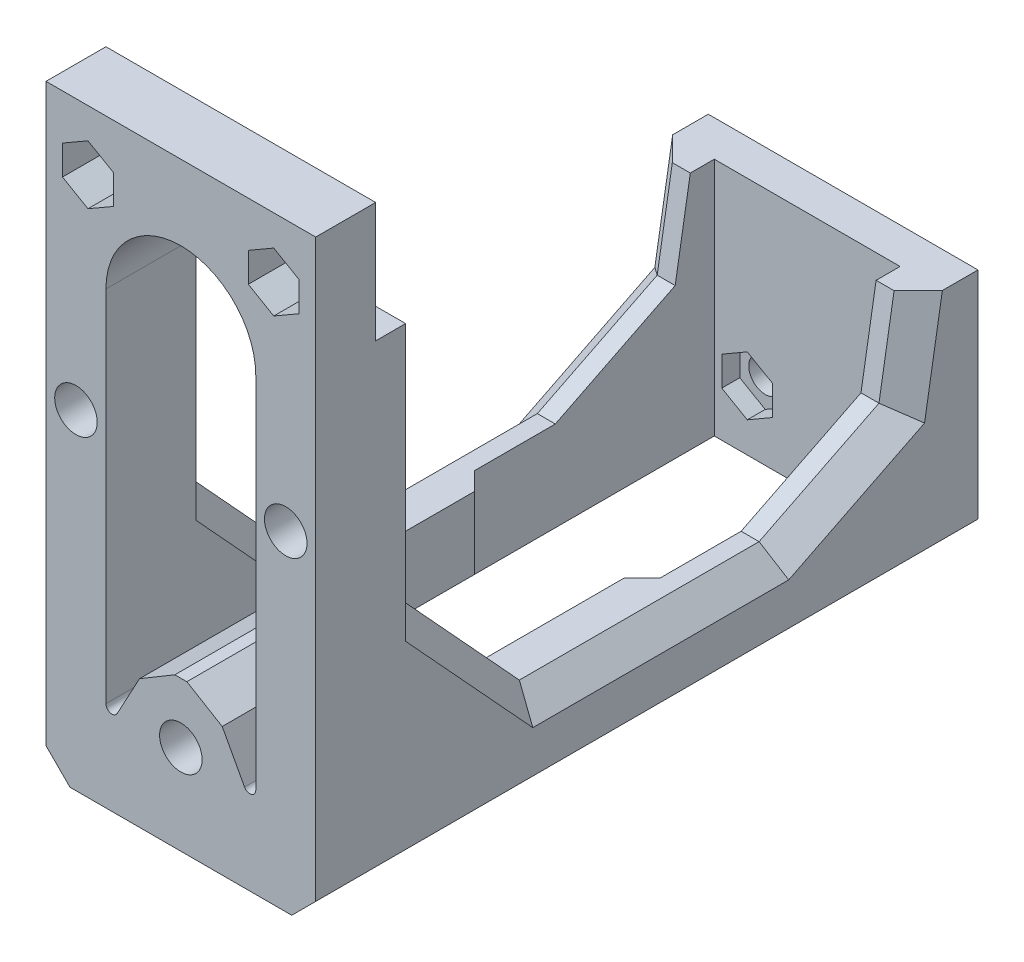
SolidWorks part; units mm, degrees
ref_plane "Front Plane" through (0, 0, 0) normal (0, 0, 1) x (1, 0, 0)
ref_plane "Top Plane" through (0, 0, 0) normal (0, 1, 0) x (1, 0, 0)
ref_plane "Right Plane" through (0, 0, 0) normal (1, 0, 0) x (0, 0, -1)
sketch "Sketch1" plane through (0, 0, 0) normal (0, 1, 0) x (1, 0, 0)
  line L0 (0, 0) -> (0, -29.9339) construction
  line L1 (-22.5, 0) -> (-12.5, 0)
  line L2 (-22.5, 0) -> (-22.5, -110.5)
  line L3 (-22.5, -110.5) -> (-12.5, -110.5)
  line L4 (-12.5, 0) -> (-12.5, -110.5)
  line L5 (-22.5, 0) -> (-12.5, -110.5) construction
  line L6 (-22.5, -110.5) -> (-12.5, 0) construction
  line L7 (22.5, -110.5) -> (12.5, -110.5)
  line L8 (12.5, 0) -> (12.5, -110.5)
  line L9 (22.5, 0) -> (12.5, 0)
  line L10 (22.5, 0) -> (22.5, -110.5)
  point P0 (-17.5, -55.25)
  dimension "D1" = 110.5
  dimension "D2" = 10
  dimension "D3" = 12.5
extrude "Boss-Extrude1" add sketch "Sketch1" along normal blind 100
sketch "Sketch2" plane through (0, 0, 0) normal (0, 0, -1) x (-1, 0, 0)
  line L0 (12.5, 0) -> (22.5, 0) construction
  line L1 (-22.5, 40) -> (22.5, 40)
  line L2 (-22.5, 40) -> (-22.5, 0)
  line L3 (-22.5, 0) -> (22.5, 0)
  line L4 (22.5, 40) -> (22.5, 0)
  line L5 (-22.5, 40) -> (22.5, 0) construction
  line L6 (-22.5, 0) -> (22.5, 40) construction
  line L7 (-22.5, 100) -> (-22.5, 0) construction
  line L8 (22.5, 100) -> (22.5, 0) construction
  point P0 (0, 20)
  dimension "D1" = 40
extrude "Boss-Extrude2" add sketch "Sketch2" against normal blind 6
sketch "Sketch3" plane through (-22.5, 0, 0) normal (-1, 0, 0) x (0, 0, 1)
  line L0 (95.5, 121.1423) -> (95.5, 40)
  line L1 (95.5, 40) -> (72.5237, 15)
  line L2 (72.5237, 15) -> (32.5237, 15)
  line L3 (32.5237, 15) -> (12.5237, 25)
  line L4 (12.5237, 25) -> (10, 40)
  line L5 (10, 40) -> (0, 40)
  line L6 (0, 100) -> (0, 0) construction
  line L7 (0, 0) -> (110.5, 0) construction
  line L8 (110.5, 100) -> (110.5, 0) construction
  line L9 (95.5, 121.1423) -> (-7.9843, 121.1423)
  line L10 (-7.9843, 121.1423) -> (-7.9843, 40)
  line L11 (-7.9843, 40) -> (0, 40)
  dimension "D1" = 40
  dimension "D2" = 15
  dimension "D3" = 25
  dimension "D4" = 20
  dimension "D5" = 10
  dimension "D6" = 15
  dimension "D7" = 40
  dimension "D8" = 40
extrude "Cut-Extrude1" cut sketch "Sketch3" against normal through all both and the other way through all
chamfer "Chamfer1" distance 4 angle 45 10 edges at (-12.5, 27.5, 84.0118) (12.5, 27.5, 84.0118) (22.5, 32.5, 11.2618) (22.5, 27.5, 84.0118) (22.5, 15, 52.5237) (22.5, 20, 22.5237) (-22.5, 32.5, 11.2618) (-22.5, 27.5, 84.0118)
chamfer "Chamfer2" distance 4 angle 45 2 edges at (22.5, 0, 55.25) (-22.5, 0, 55.25)
sketch "Sketch4" plane through (0, 0, 0) normal (0, 0, -1) x (-1, 0, 0)
  line L0 (-18.5, 0) -> (18.5, 0) construction
  line L1 (0, 0) -> (0, 25.518) construction
  circle A0 centre (-10, 10) radius 2.75
  circle A1 centre (10, 10) radius 2.75
  dimension "D3" = 5.5
  dimension "D1" = 10
  dimension "D2" = 10
extrude "Cut-Extrude2" cut sketch "Sketch4" against normal up to surface (6 mm away) and the other way through all up to face at (0, 20, 6)
sketch "Sketch5" plane through (0, 0, 6) normal (0, 0, 1) x (1, 0, 0)
  line L1 (-10, 14.9075) -> (-14.25, 12.4537)
  line L2 (-14.25, 12.4537) -> (-14.25, 7.5463)
  line L3 (-14.25, 7.5463) -> (-10, 5.0925)
  line L4 (-10, 5.0925) -> (-5.75, 7.5463)
  line L5 (-5.75, 7.5463) -> (-5.75, 12.4537)
  line L6 (-5.75, 12.4537) -> (-10, 14.9075)
  line L7 (10, 14.9075) -> (5.75, 12.4537)
  line L8 (5.75, 12.4537) -> (5.75, 7.5463)
  line L9 (5.75, 7.5463) -> (10, 5.0925)
  line L10 (10, 5.0925) -> (14.25, 7.5463)
  line L11 (14.25, 7.5463) -> (14.25, 12.4537)
  line L12 (14.25, 12.4537) -> (10, 14.9075)
  circle A0 centre (-10, 10) radius 4.25 construction
  circle A1 centre (10, 10) radius 4.25 construction
  arc A2 (-12.5, 8.8544) -> (-12.5, 11.1456) centre (-10, 10) ccw construction
  arc A3 (12.5, 11.1456) -> (12.5, 8.8544) centre (10, 10) ccw construction
  dimension "D1" = 8.5
extrude "Cut-Extrude3" cut sketch "Sketch5" against normal offset from surface 3 and the other way blind 10 up to face at (12.75, 10, 0)
sketch "Sketch6" plane through (0, 40, 0) normal (0, 1, 0) x (1, 0, 0)
  line L1 (-15.5, -46) -> (15.5, -46)
  line L2 (-15.5, -46) -> (-15.5, -6)
  line L3 (-15.5, -6) -> (15.5, -6)
  line L4 (15.5, -46) -> (15.5, -6)
  line L5 (-15.5, -46) -> (15.5, -6) construction
  line L6 (-15.5, -6) -> (15.5, -46) construction
  line L7 (-18.5, -12.5237) -> (-18.5, -32.5237) construction
  line L8 (-12.5, -6) -> (12.5, -6) construction
  point P0 (0, -26)
  point P7 (0, 0)
  point P11 (0, 0)
  dimension "D1" = 3
  dimension "D2" = 40
extrude "Cut-Extrude4" cut sketch "Sketch6" against normal through all both and the other way through all
chamfer "Chamfer4" distance 3 angle 45 4 edges at (12.5, 0, 78.25) (12.5, 7.5, 46) (-12.5, 0, 78.25) (-12.5, 7.5, 46)
sketch "Sketch7" plane through (0, 0, 110.5) normal (0, 0, 1) x (1, 0, 0)
  line L0 (-12.5, 100) -> (-12.5, 3) construction
  line L1 (12.5, 100) -> (12.5, 3) construction
  line L2 (-15.5, 40) -> (15.5, 40) construction
  line L3 (-22.5, 100) -> (22.5, 100)
  line L4 (22.5, 100) -> (12.5, 75)
  line L6 (-12.5, 75) -> (-22.5, 100)
  arc A0 (12.5, 75) -> (-12.5, 75) centre (0, 75) ccw
  dimension "D1" = 35
extrude "Boss-Extrude3" add sketch "Sketch7" against normal up to surface (15 mm away) up to face at (17.5, 58.0296, 95.5)
sketch "Sketch8" plane through (0, 0, 110.5) normal (0, 0, 1) x (1, 0, 0)
  line L0 (-22.5, 100) -> (-22.5, 4) construction
  line L1 (-22.5, 100) -> (22.5, 100) construction
  line L2 (22.5, 100) -> (22.5, 4) construction
  circle A0 centre (-15.5, 90) radius 2.75
  circle A1 centre (15.5, 90) radius 2.75
  dimension "D3" = 10
  dimension "D5" = 5.5
  dimension "D1" = 7
  dimension "D2" = 10
  dimension "D4" = 7
extrude "Cut-Extrude5" cut sketch "Sketch8" against normal through all both and the other way through all
sketch "Sketch10" plane through (0, 0, 95.5) normal (0, 0, -1) x (-1, 0, 0)
  line L0 (22.5, 40) -> (-22.5, 40) construction
  line L1 (-12.5, 75) -> (-12.5, 34.0888) construction
  line L2 (12.5, 34.0888) -> (12.5, 75) construction
  circle A0 centre (-17.5, 55) radius 3.55
  circle A1 centre (17.5, 55) radius 3.55
  dimension "D1" = 7.1
  dimension "D2" = 15
  dimension "D3" = 5
  dimension "D4" = 5
extrude "Cut-Extrude7" cut sketch "Sketch10" against normal through all both and the other way through all
sketch "Sketch11" plane through (0, 0, 95.5) normal (0, 0, -1) x (-1, 0, 0)
  circle A0 centre (-17.5, 55) radius 4.5
  circle A1 centre (17.5, 55) radius 4.5
  dimension "D1" = 9
extrude "Cut-Extrude8" cut sketch "Sketch11" against normal offset from surface (6 mm away) 9 up to face at (17.5, 58.55, 110.5)
sketch "Sketch12" plane through (0, 0, 95.5) normal (0, 0, -1) x (-1, 0, 0)
  line L0 (-22.5, 100) -> (22.5, 100) construction
  line L1 (-27.382, 104.523) -> (28.3636, 104.523)
  line L2 (-27.382, 104.523) -> (-27.382, 80)
  line L3 (-27.382, 80) -> (28.3636, 80)
  line L4 (28.3636, 104.523) -> (28.3636, 80)
  line L5 (-27.382, 104.523) -> (28.3636, 80) construction
  line L6 (-27.382, 80) -> (28.3636, 104.523) construction
  point P0 (0.4908, 92.2615)
  dimension "D1" = 20
extrude "Cut-Extrude9" cut sketch "Sketch12" against normal offset from surface (5 mm away) 10 up to face at (17.5, 58.55, 110.5)
sketch "Sketch9" plane through (0, 0, 110.5) normal (0, 0, 1) x (1, 0, 0)
  line L1 (-15.5, 94.9075) -> (-19.75, 92.4537)
  line L2 (-19.75, 92.4537) -> (-19.75, 87.5463)
  line L3 (-19.75, 87.5463) -> (-15.5, 85.0925)
  line L4 (-15.5, 85.0925) -> (-11.25, 87.5463)
  line L5 (-11.25, 87.5463) -> (-11.25, 92.4537)
  line L6 (-11.25, 92.4537) -> (-15.5, 94.9075)
  line L7 (15.5, 94.9075) -> (11.25, 92.4537)
  line L8 (11.25, 92.4537) -> (11.25, 87.5463)
  line L9 (11.25, 87.5463) -> (15.5, 85.0925)
  line L10 (15.5, 85.0925) -> (19.75, 87.5463)
  line L11 (19.75, 87.5463) -> (19.75, 92.4537)
  line L12 (19.75, 92.4537) -> (15.5, 94.9075)
  circle A0 centre (-15.5, 90) radius 4.25 construction
  circle A1 centre (15.5, 90) radius 4.25 construction
  dimension "D1" = 8.5
extrude "Cut-Extrude6" cut sketch "Sketch9" against normal offset from surface (7 mm away) 3 up to face at (12.75, 90, 100.5)
sketch "Sketch13" plane through (0, 0, 101.5) normal (0, 0, -1) x (-1, 0, 0)
  circle A0 centre (-17.5, 55) radius 2.75
  circle A1 centre (17.5, 55) radius 2.75
  circle A2 centre (-17.5, 55) radius 3.55 construction
  circle A3 centre (17.5, 55) radius 3.55 construction
  circle A4 centre (-17.5, 55) radius 4.5
  circle A5 centre (17.5, 55) radius 4.5
  circle A6 centre (-17.5, 55) radius 4.5 construction
  circle A7 centre (17.5, 55) radius 4.5 construction
  dimension "D1" = 5.5
  dimension "D2" = 5.5
extrude "Boss-Extrude4" add sketch "Sketch13" along normal blind 3
sketch "Sketch14" plane through (0, 0, 110.5) normal (0, 0, 1) x (1, 0, 0)
  line L0 (15.5, 0) -> (-15.5, 0) construction
  line L1 (-5, 25) -> (5, 25)
  line L3 (-18.5, 0) -> (18.5, 0)
  line L5 (-8.6089, 18.3168) -> (18.5, 0) construction
  line L6 (-18.5, 0) -> (8.6089, 18.3168) construction
  line L7 (18.5, 0) -> (5, 25)
  line L8 (-18.5, 0) -> (-5, 25)
  point P0 (0, 12.5)
  dimension "D2" = 10
  dimension "D3" = 5
extrude "Boss-Extrude5" add sketch "Sketch14" against normal blind 20
chamfer "Chamfer5" distance 5 angle 45 1 edges at (0, 0, 90.5)
sketch "Sketch15" plane through (0, 0, 90.5) normal (0, 0, -1) x (-1, 0, 0)
  line L0 (-18.5, 0) -> (18.5, 0) construction
  line L1 (22.5, 100) -> (22.5, 4) construction
  circle A0 centre (0, 15) radius 2.75
  circle A1 centre (-15.5, 90) radius 2.75 construction
  dimension "D1" = 15
  dimension "D2" = 22.5
extrude "Cut-Extrude11" cut sketch "Sketch15" against normal through all
sketch "Sketch16" plane through (0, 0, 110.5) normal (0, 0, 1) x (1, 0, 0)
  circle A0 centre (0, 15) radius 3.55
  circle A2 centre (0, 15) radius 2.75 construction
  dimension "D1" = 7.1
extrude "Cut-Extrude12" cut sketch "Sketch16" against normal offset from surface (9 mm away) 9 up to face at (-2.75, 15, 110.5)
sketch "Sketch17" plane through (0, 0, 90.5) normal (0, 0, -1) x (-1, 0, 0)
  circle A0 centre (0, 15) radius 5
  circle A1 centre (0, 15) radius 2.75 construction
  dimension "D1" = 10
extrude "Cut-Extrude13" cut sketch "Sketch17" against normal blind 5
chamfer "Chamfer6" distance 4 2 edges at (5, 25, 100.5) (-5, 25, 100.5)
fillet "Fillet1" radius 1 2 edges at (12.5, 11.1111, 100.5) (-12.5, 11.1111, 100.5)
